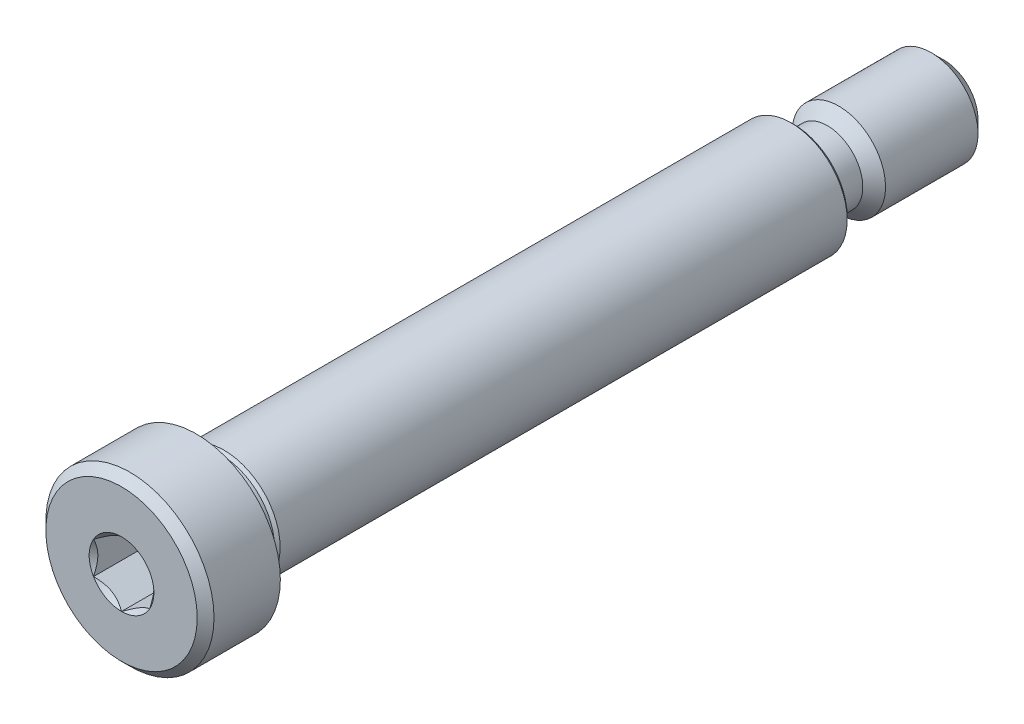
SolidWorks part; units mm, degrees
material "Alloy Steel"
ref_plane "Front Plane" through (0, 0, 0) normal (0, 0, 1) x (1, 0, 0)
ref_plane "Top Plane" through (0, 0, 0) normal (0, 1, 0) x (1, 0, 0)
ref_plane "Right Plane" through (0, 0, 0) normal (1, 0, 0) x (0, 0, -1)
sketch "Sketch2" plane through (0, 0, 0) normal (1, 0, 0) x (0, 0, -1)
  line L0 (-34.925, 0) -> (34.925, 0) construction
  line L1 (-34.925, 0) -> (-34.925, 7.1437)
  line L2 (-34.925, 7.1437) -> (-28.575, 7.1438)
  line L3 (-28.575, 7.1438) -> (-28.575, 4.7625)
  line L4 (-28.575, 4.7625) -> (22.225, 4.7625)
  line L5 (22.225, 3.9751) -> (34.925, 3.9751)
  line L6 (34.925, 3.9751) -> (34.925, 0)
  line L7 (34.8368, 4.1279) -> (35.5424, 2.9058) construction
  line L8 (35.5424, 2.9058) -> (36.2479, 4.1279) construction
  line L9 (36.2479, 4.1279) -> (34.8368, 4.1279) construction
  line L10 (34.925, 3.9751) -> (36.1597, 3.9751) construction
  line L11 (35.5424, 4.1279) -> (35.5424, 3.9751) construction
  line L12 (35.5424, 3.9751) -> (35.5424, 3.0586) construction
  line L13 (35.5424, 3.0586) -> (35.5424, 2.9058) construction
  line L14 (35.4542, 3.0586) -> (35.6306, 3.0586)
  line L15 (34.8809, 4.0515) -> (36.2038, 4.0515)
  line L16 (35.6306, 3.0586) -> (36.2038, 4.0515)
  line L17 (35.4542, 3.0586) -> (34.8809, 4.0515)
  line L18 (34.925, 0) -> (34.925, -3.9751) construction
  line L19 (22.225, -4.7625) -> (22.225, 0) construction
  line L20 (22.225, 0) -> (22.225, 4.7625) construction
  line L21 (-34.925, 0) -> (-34.925, -7.1437) construction
  point P11 (-26.2128, 4.7625)
  point P12 (31.3972, -3.9751)
  point P22 (35.5424, 4.0515)
  point P23 (17.145, 0)
  point P25 (-21.1328, 0)
  point P26 (-28.575, -7.1437)
  point P29 (22.225, -4.7625)
  dimension "Head Height" = 6.35
  dimension "Shoulder Diameter" = 9.525
  dimension "Screw Size Decimal Equivalent" = 7.9502
  dimension "Thread Length" = 12.7
  dimension "Head Diameter" = 14.2875
  dimension "Undercut Length" = 2.3622
  dimension "Pitch" = 1.4111
  dimension "D2" = 0.1764
  dimension "D1" = 3.5278
  dimension "Shoulder Length" = 50.8
  dimension "D4" = 5.08
  dimension "D3" = 5.08
sketch "Sketch3" plane through (0, 0, 0) normal (0, 0, 1) x (1, 0, 0)
  line L1 (0, 2.7496) -> (-2.3813, 1.3748)
  line L2 (-2.3813, 1.3748) -> (-2.3813, -1.3748)
  line L3 (-2.3813, -1.3748) -> (0, -2.7496)
  line L4 (0, -2.7496) -> (2.3812, -1.3748)
  line L5 (2.3812, -1.3748) -> (2.3812, 1.3748)
  line L6 (2.3812, 1.3748) -> (0, 2.7496)
  circle A0 centre (0, 0) radius 2.3813 construction
  dimension "Drive Size" = 4.7625
sketch "Sketch4" plane through (0, 0, 0) normal (1, 0, 0) x (0, 0, -1)
  line L0 (-28.575, 7.1438) -> (-34.2106, 7.1437)
  line L1 (-34.2106, 7.1437) -> (-34.925, 6.4294)
  line L2 (-28.575, 7.1438) -> (-28.575, 4.7625)
  line L3 (-28.575, 4.7625) -> (-28.3369, 4.5244)
  line L4 (-28.3369, 4.5244) -> (-26.4509, 4.5244)
  line L5 (-26.4509, 4.5244) -> (-26.2128, 4.7625)
  line L6 (-28.575, 4.7625) -> (22.225, 4.7625) construction
  line L7 (-34.925, 0) -> (34.925, 0) construction
  line L8 (-26.2128, 4.7625) -> (21.9625, 4.7625)
  line L9 (21.9625, 4.7625) -> (22.225, 4.5)
  line L10 (22.225, 4.5) -> (22.225, 0)
  line L11 (22.225, 4.7625) -> (22.225, 4.5) construction
  line L12 (22.225, 4.5) -> (22.225, 4.2376) construction
  line L13 (22.225, 4.2376) -> (22.225, 3.9751) construction
  line L14 (-34.925, 6.4294) -> (-34.925, 0)
  line L15 (-34.925, 7.1437) -> (-28.575, 7.1438) construction
  line L16 (-34.925, 0) -> (22.225, 0)
  dimension "D1" = 45
  dimension "D2" = 9.0487
  dimension "D3" = 45
  dimension "D4" = 45
  dimension "D5" = 12.8587
revolve "Revolve1" add sketch "Sketch4" angle 360 about L16
sketch "Sketch5" plane through (0, 0, 34.925) normal (0, 0, 1) x (1, 0, 0)
  line L0 (2.3812, 1.3748) -> (0, 2.7496) construction
  line L1 (2.3812, -1.3748) -> (2.3812, 1.3748) construction
  line L2 (0, -2.7496) -> (2.3812, -1.3748) construction
  line L3 (-2.3813, -1.3748) -> (0, -2.7496) construction
  line L4 (-2.3813, 1.3748) -> (-2.3813, -1.3748) construction
  line L5 (0, 2.7496) -> (-2.3813, 1.3748) construction
  line L6 (2.3812, 1.3748) -> (0, 2.7496)
  line L7 (2.3812, -1.3748) -> (2.3812, 1.3748)
  line L8 (0, -2.7496) -> (2.3812, -1.3748)
  line L9 (-2.3813, -1.3748) -> (0, -2.7496)
  line L10 (-2.3813, 1.3748) -> (-2.3813, -1.3748)
  line L11 (0, 2.7496) -> (-2.3813, 1.3748)
extrude "Cut-Extrude1" cut sketch "Sketch5" against normal blind 4.7625
sketch "Sketch6" plane through (0, 0, 34.925) normal (0, 0, 1) x (1, 0, 0)
  circle A0 centre (0, 0) radius 2.7496
extrude "Cut-Extrude4" cut sketch "Sketch6" against normal blind 4.7625 draft 45
sketch "Sketch7" plane through (0, 0, 0) normal (1, 0, 0) x (0, 0, -1)
  line L0 (22.225, 3.9751) -> (33.8667, 3.9751)
  line L1 (22.225, 3.9751) -> (34.925, 3.9751) construction
  line L2 (33.8667, 3.9751) -> (34.925, 2.9168)
  line L3 (34.925, 3.9751) -> (34.925, 0) construction
  line L4 (34.925, 2.9168) -> (34.925, 0)
  line L5 (34.925, 0) -> (22.225, 0)
  line L6 (22.225, -4.5) -> (22.225, 4.5) construction
  line L7 (22.225, 0) -> (22.225, 3.9751)
  dimension "D1" = 45
  dimension "D2" = 1.0583
revolve "Revolve2" add sketch "Sketch7" angle 360 about L5
sketch "Sketch10" plane through (0, 0, 0) normal (1, 0, 0) x (0, 0, -1)
  line L0 (23.1902, 3.0099) -> (25.0444, 3.0099)
  line L1 (25.0444, 3.0099) -> (26.797, 4.7625)
  line L2 (26.797, 4.7625) -> (22.225, 4.7625)
  line L3 (22.225, 4.7625) -> (22.225, 3.9751)
  line L4 (22.225, -4.5) -> (22.225, 4.5) construction
  line L5 (34.925, 0) -> (22.225, 0) construction
  line L6 (-34.925, 0) -> (34.925, 0) construction
  arc A0 (22.225, 3.9751) -> (23.1902, 3.0099) centre (23.1902, 3.9751) ccw
  dimension "Flat OD" = 6.0198
  dimension "Flat" = 2.8194
  dimension "D3" = 45
revolve "Cut-Revolve1" cut sketch "Sketch10" angle 360 about L5
sketch "Sketch8" [suppressed] plane through (0, 0, -34.925) normal (0, 0, -1) x (-1, 0, 0)
  circle A0 centre (0, 0) radius 3.9751 construction
  circle A1 centre (0, 0) radius 3.9751
curve "Helix/Spiral1" [suppressed] pitch 1.4111 height 14.1111 turns 10
sketch "Sketch9" [suppressed] plane through (0, 0, 0) normal (1, 0, 0) x (0, 0, -1)
  line L0 (35.4542, 3.0586) -> (35.6306, 3.0586) construction
  line L1 (35.6306, 3.0586) -> (36.2038, 4.0515) construction
  line L2 (34.8809, 4.0515) -> (36.2038, 4.0515) construction
  line L3 (35.4542, 3.0586) -> (34.8809, 4.0515) construction
  line L4 (35.4542, 3.0586) -> (35.6306, 3.0586)
  line L5 (35.6306, 3.0586) -> (36.2038, 4.0515)
  line L6 (34.8809, 4.0515) -> (36.2038, 4.0515)
  line L7 (35.4542, 3.0586) -> (34.8809, 4.0515)
ref_plane "Plane1" [suppressed] through (0, 0, -25.0444) normal (0, 0, 1) x (1, 0, 0)
split "Split1" [suppressed] bodies to split 138
sweep "Cut-Sweep1" [suppressed] cut profiles "Sketch9" path "Helix/Spiral1"
combine bodies "Combine1" [suppressed] operation type add bodies to combine 141 139
sketch "Sketch11" [suppressed] plane through (0, 0, 34.925) normal (0, 0, 1) x (1, 0, 0)
  line L0 (-0.1031, 7.1437) -> (0.1031, 7.1437)
  line L1 (0.1031, 7.1437) -> (0, 6.9652)
  line L2 (0, 0) -> (0, 7.1437) construction
  line L3 (0, 6.9652) -> (-0.1031, 7.1437)
  line L4 (0, 0) -> (7.1437, 0) construction
  circle A0 centre (0, 0) radius 7.1437 construction
  point P6 (0, 7.1437)
  dimension "D1" = 13.9303
  dimension "D2" = 60
  dimension "D3" = 0.2062
sketch "Sketch12" [suppressed] plane through (0, 0, 0) normal (1, 0, 0) x (0, 0, -1)
  line L0 (-34.925, 6.9652) -> (-30.5937, 6.9652)
  line L1 (-29.9839, 7.5749) -> (-29.9839, 7.1437) construction
  line L2 (-34.925, 7.1437) -> (-28.575, 7.1437) construction
  arc A0 (-30.5937, 6.9652) -> (-29.9839, 7.5749) centre (-30.5937, 7.5749) ccw
  point P11 (-30.1625, 7.1438)
  dimension "D1" = 1.5875
sweep "Cut-Sweep2" [suppressed] cut profiles "Sketch11" path "Sketch12"
pattern_circular "CirPattern1" [suppressed] count 76 over 360 about axis through (0, 0, 34.925) along (0, 0, -1) of bodies 143
equation "\"D2@Sketch2\" = \"Pitch@Sketch2\" / 8"
equation "\"D1@Sketch2\"=\"Pitch@Sketch2\"*2.5"
equation "\"D2@Sketch4\"=\"Shoulder Diameter@Sketch2\"*0.95"
equation "\"D5@Sketch4\"=\"Head Diameter@Sketch2\"*0.9"
equation "\"D1@Cut-Extrude1\"=\"Head Height@Sketch2\"*0.75"
equation "\"D1@Cut-Extrude4\"=\"D1@Cut-Extrude1\""
equation "\"D2@Sketch7\"=\"pitch@sketch2\"*0.75"
equation "\"D3@Helix/Spiral1\"=\"Thread Length@Sketch2\"+\"Pitch@Sketch2\""
equation "\"D4@Helix/Spiral1\"=\"Pitch@Sketch2\""
equation "\"D1@Sketch11\"=\"Head Diameter@Sketch2\"*0.975"
equation "\"D1@Sketch12\"=\"Head Height@Sketch2\"*0.25"
equation "\"D1@CirPattern1\"=\"Head Diameter@Sketch2\" * 3.14 / \"D3@Sketch11\" * 0.35"
equation "\"D3@Sketch2\"=\"D4@Sketch2\""
equation "\"D4@Sketch2\"=IF(\"Shoulder Length@Sketch2\"<.5,.1,(\"Shoulder Length@Sketch2\"*.1))"
